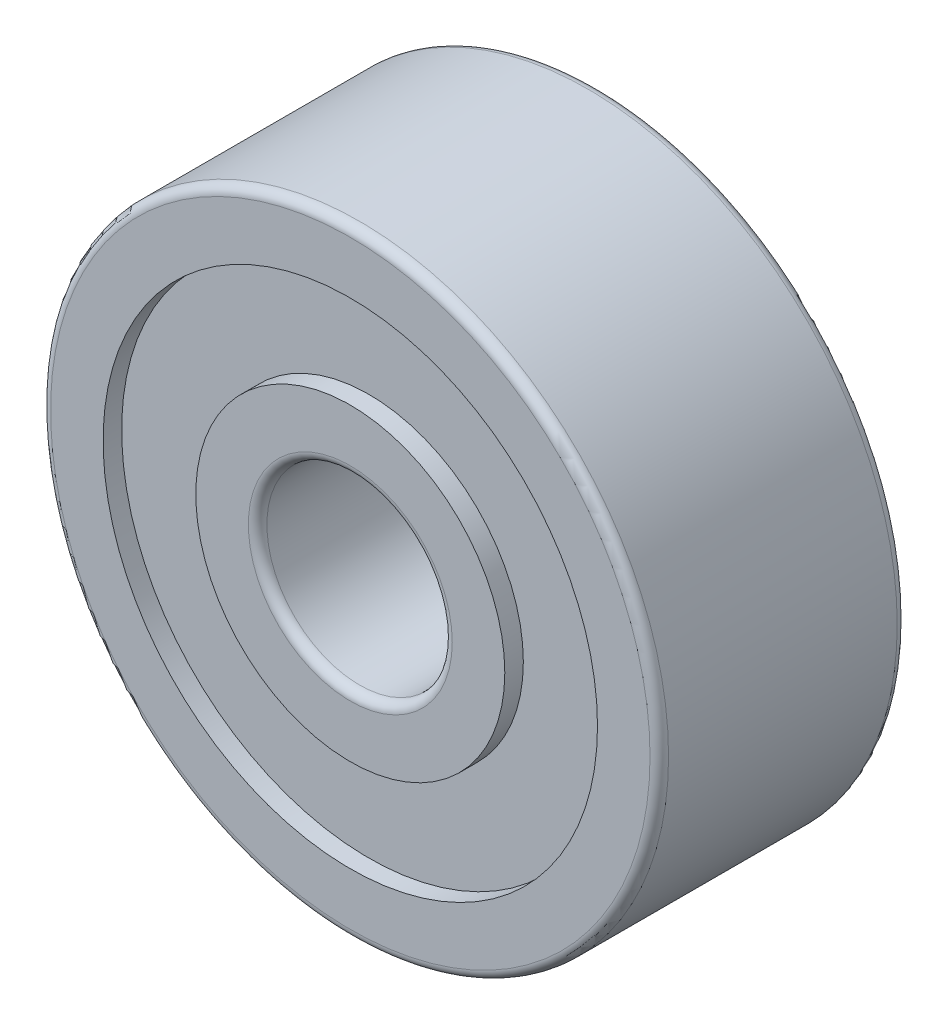
SolidWorks part; units mm, degrees
ref_plane "Спереди" through (0, 0, 0) normal (0, 0, 1) x (1, 0, 0)
ref_plane "Сверху" through (0, 0, 0) normal (0, 1, 0) x (1, 0, 0)
ref_plane "Справа" through (0, 0, 0) normal (1, 0, 0) x (0, 0, -1)
sketch "Эскиз1" plane through (0, 0, 0) normal (0, 0, 1) x (1, 0, 0)
  circle A0 centre (-407.6519, 139.3726) radius 5
  circle A1 centre (-407.6519, 139.3726) radius 1.5
extrude "Бобышка-Вытянуть1" add sketch "Эскиз1" against normal blind 4
sketch "Эскиз2" plane through (0, 0, 0) normal (0, 0, 1) x (1, 0, 0)
  circle A0 centre (-407.6519, 139.3726) radius 2.5
  circle A1 centre (-407.6519, 139.3726) radius 4
extrude "Вырез-Вытянуть1" cut sketch "Эскиз2" against normal blind 0.3
extrude "Вырез-Вытянуть3" cut sketch "Эскиз2<2>" along normal blind 0.3 from surface starting at face at (-406.1519, 139.3726, -4)
sketch "Эскиз2<2>" plane through (0, 0, 0) normal (0, 0, 1) x (1, 0, 0) same geometry as "Эскиз2"
fillet "Скругление1" radius 0.15 4 edges at (-406.1519, 139.3726, -4) (-406.1519, 139.3726, 0) (-402.6519, 139.3726, -4) (-402.6519, 139.3726, 0)
